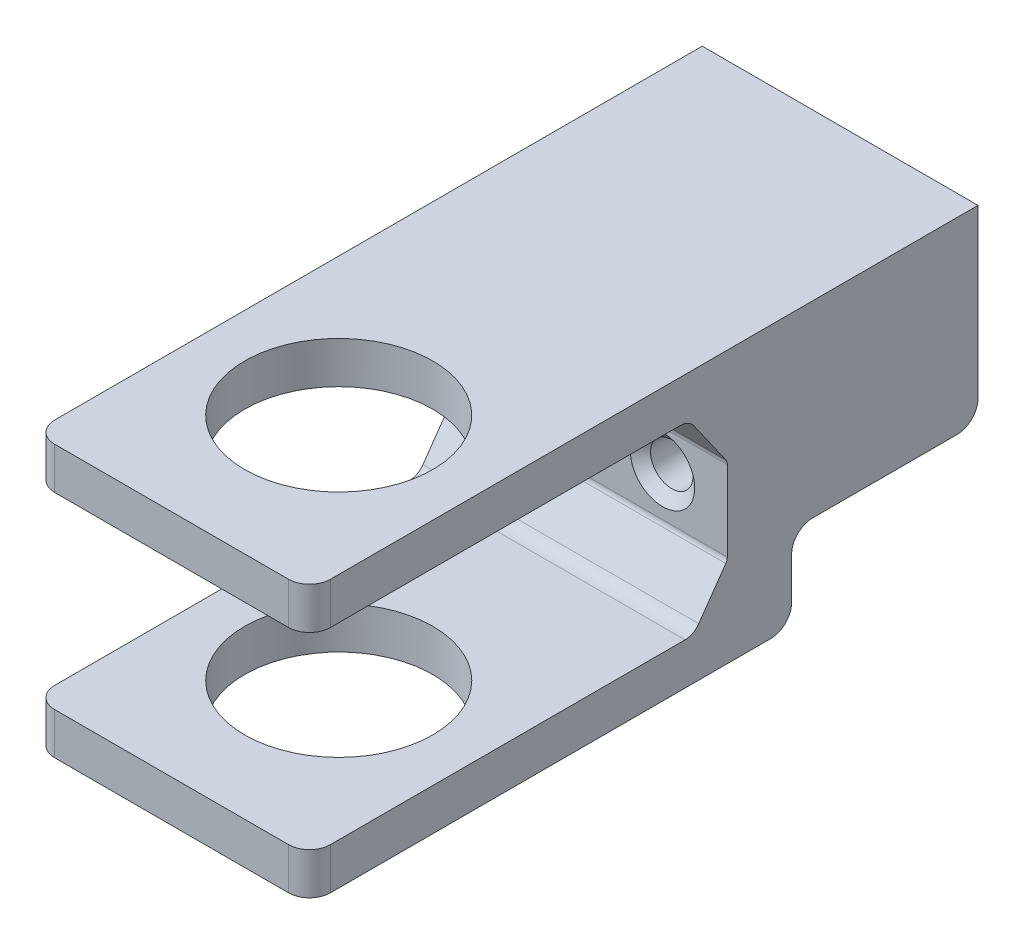
SolidWorks part; units mm, degrees
ref_plane "Front Plane" through (0, 0, 0) normal (0, 0, 1) x (1, 0, 0)
ref_plane "Top Plane" through (0, 0, 0) normal (0, 1, 0) x (1, 0, 0)
ref_plane "Right Plane" through (0, 0, 0) normal (1, 0, 0) x (0, 0, -1)
sketch "Sketch1" plane through (0, 0, 0) normal (0, 1, 0) x (1, 0, 0)
  line L1 (-20.955, -50.8) -> (20.955, -50.8)
  line L2 (-20.955, -50.8) -> (-20.955, 50.8)
  line L3 (-20.955, 50.8) -> (20.955, 50.8)
  line L4 (20.955, -50.8) -> (20.955, 50.8)
  line L5 (-20.955, -50.8) -> (20.955, 50.8) construction
  line L6 (-20.955, 50.8) -> (20.955, -50.8) construction
  point P0 (0, 0)
  dimension "D1" = 41.91
  dimension "D2" = 101.6
extrude "Boss-Extrude1" add sketch "Sketch1" along normal blind 41.275
sketch "Sketch13" plane through (-20.955, 0, 0) normal (-1, 0, 0) x (0, 0, 1)
  line L0 (-12.7, 26.6024) -> (-6.8725, 34.925)
  line L1 (-6.8725, 34.925) -> (50.8, 34.925)
  line L2 (-12.7, 26.6024) -> (-12.7, 13.6323)
  line L3 (-7.6009, 6.35) -> (50.8, 6.35)
  line L4 (-50.8, 0) -> (50.8, 0)
  line L5 (50.8, 0) -> (50.8, 41.275)
  line L6 (50.8, 41.275) -> (-50.8, 41.275)
  line L7 (-50.8, 41.275) -> (-50.8, 0)
  line L8 (-50.8, 0) -> (50.8, 0)
  line L9 (50.8, 0) -> (50.8, 41.275)
  line L10 (50.8, 41.275) -> (-50.8, 41.275)
  line L11 (-50.8, 41.275) -> (-50.8, 0)
  line L12 (50.8, 34.925) -> (50.8, 6.35)
  line L13 (-12.7, 13.6323) -> (-7.6009, 6.35)
  line M11 (50.8, 0) -> (50.8, 41.275)
  dimension "D2" = 6.35
  dimension "D3" = 38.1
  dimension "D4" = 6.35
  dimension "D5" = 10.16
  dimension "D6" = 125
  dimension "D7" = 8.89
  dimension "D8" = 57.6725
  dimension "D9" = 125
  dimension "D1" = 0
extrude "Cut-Extrude6" cut sketch "Sketch13" against normal through all contours L2 L13 L3 L1 L0 M11 region at (-20.955, 20.6042, 19.7729)
sketch "Sketch3" plane through (0, 41.275, 0) normal (0, 1, 0) x (1, 0, 0)
  line L1 (20.955, 50.8) -> (-20.955, 50.8) construction
  line L3 (2.7496, -20.6375) -> (-2.7496, -20.6375)
  line L4 (-2.7496, -20.6375) -> (-5.4993, -25.4)
  line L5 (-5.4993, -25.4) -> (-2.7496, -30.1625)
  line L6 (-2.7496, -30.1625) -> (2.7496, -30.1625)
  line L7 (2.7496, -30.1625) -> (5.4993, -25.4)
  line L8 (5.4993, -25.4) -> (2.7496, -20.6375)
  circle A0 centre (0, -25.4) radius 50.8
  circle A1 centre (0, -25.4) radius 4.7625 construction
  circle A2 centre (0, -25.4) radius 14.3002
  dimension "D1" = 101.6
  dimension "D2" = 25.4
  dimension "D3" = 9.525
  dimension "D4" = 28.6004
extrude "Cut-Extrude2" cut sketch "Sketch3" against normal through all contours L7 L8 L3 L4 L5 L6 | A2 L8 L7 L6 L5 L4 L3 region at (0, 41.275, 25.4) region at (-13.8957, 41.275, 25.4)
sketch "Sketch17" plane through (-20.955, 0, 0) normal (-1, 0, 0) x (0, 0, 1)
  line L11 (-50.8, 41.275) -> (-50.8, 0) construction
  line L16 (-50.8, 0) -> (-22.479, 0)
  line L17 (-50.8, 0) -> (-50.8, 12.7)
  line L18 (-50.8, 12.7) -> (-22.479, 12.7)
  line L19 (-22.479, 0) -> (-22.479, 12.7)
  line L20 (-50.8, 0) -> (50.8, 0) construction
  dimension "D1" = 28.321
  dimension "D2" = 12.7
extrude "Cut-Extrude7" cut sketch "Sketch17" against normal through all
sketch "Sketch4" plane through (0, 0, -50.8) normal (0, 0, -1) x (-1, 0, 0)
  line L0 (-20.955, 20.6375) -> (20.955, 20.6375) construction
  line L1 (-20.955, 41.275) -> (-20.955, 12.7) construction
  line L3 (11.1125, 20.6375) -> (-11.1125, 20.6375) construction
  line L4 (-20.955, 41.275) -> (20.955, 41.275) construction
  circle A0 centre (11.1125, 20.6375) radius 3.2258
  circle A1 centre (-11.1125, 20.6375) radius 3.2258
  point P10 (0, 20.6375)
  point P12 (0, 20.6375)
  dimension "D1" = 6.4516
  dimension "D2" = 22.225
  dimension "D3" = 20.6375
  dimension "D4" = 41.91
extrude "Cut-Extrude3" cut sketch "Sketch4" against normal through all
fillet "Fillet2" radius 3.175 7 edges at (-20.955, 3.175, 50.8) (20.955, 3.175, 50.8) (-20.955, 38.1, 50.8) (20.955, 38.1, 50.8) (0, 12.7, -50.8) (0, 0, -22.479) (0, 12.7, -22.479)
hole_wizard "CSK for #10 Flat Head Machine Screw (100)4" positions "Sketch14" profile "Sketch15" countersink size "#10" standard "ANSI Inch"
sketch "Sketch14" plane through (0, 0, -12.7) normal (0, 0, 1) x (1, 0, 0)
  point P0 (-11.1125, 20.6375)
  point P3 (11.1125, 20.6375)
sketch "Sketch15" plane through (-11.1125, 20.6375, -12.7) normal (1, 0, 0) x (0, -1, 0)
  line L0 (0, 0) -> (0, 39.7864)
  line L1 (0, 39.7864) -> (2.8067, 38.1)
  line L2 (2.8067, 38.1) -> (2.8067, 1.7477)
  line L3 (2.8067, 1.7477) -> (4.8895, 0)
  line L5 (4.8895, 0) -> (0, 0)
  line L6 (-2.8067, 1.7477) -> (-4.8895, 0) construction
  line L10 (0, 39.7864) -> (-2.8067, 38.1) construction
  line L11 (0, -6.35) -> (0, 107.95) construction
  dimension "Hole Dia." = 5.6134
  dimension "Hole Depth" = 38.1
  dimension "Near C'Sink Dia." = 9.779
  dimension "Near C'Sink Angle" = 100
  dimension "Drill Angle" = 118
fillet "Fillet3" radius 2.54 2 edges at (0, 6.35, -7.6009) (0, 34.925, -6.8725)
fillet "Fillet4" radius 1.27 2 edges at (0, 13.6323, -12.7) (0, 26.6024, -12.7)
